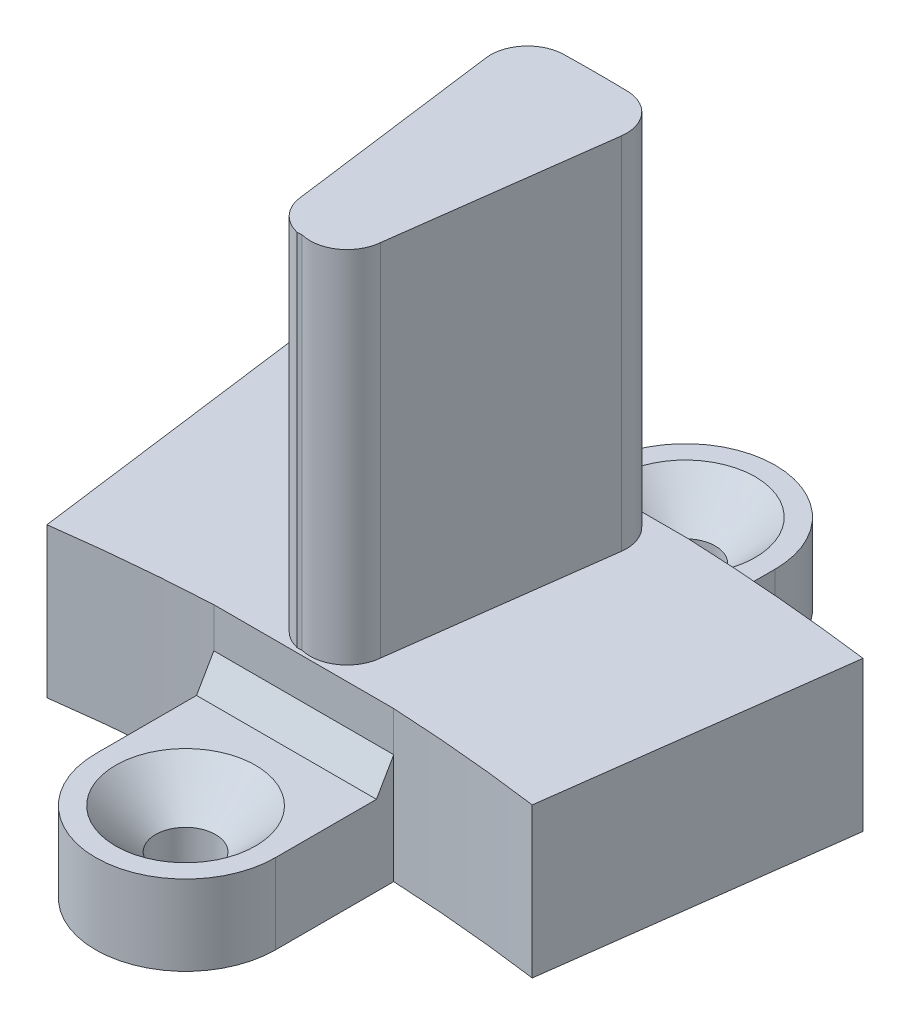
SolidWorks part; units mm, degrees
ref_plane "Front Plane" through (0, 0, 0) normal (0, 0, 1) x (1, 0, 0)
ref_plane "Top Plane" through (0, 0, 0) normal (0, 1, 0) x (1, 0, 0)
ref_plane "Right Plane" through (0, 0, 0) normal (1, 0, 0) x (0, 0, -1)
sketch "Sketch1" plane through (0, 0, 0) normal (0, 1, 0) x (1, 0, 0)
  line L0 (-42.0952, 101.6267) -> (-34.716, 83.8117) construction
  line L1 (34.716, 83.8117) -> (42.0952, 101.6267) construction
  line L2 (0, 90.7172) -> (0, 171.0298) construction
  line L3 (-34.716, 83.8117) -> (0, 0) construction
  line L4 (0, 0) -> (0, 90.7172) construction
  line L5 (0, 0) -> (34.716, 83.8117) construction
  line L6 (14.0642, 106.8282) -> (12.1389, 92.2044) construction
  line L7 (-14.0642, 106.8282) -> (-12.1389, 92.2044) construction
  line L8 (-14.0642, 106.8282) -> (-12.1389, 92.2044)
  line L9 (12.1389, 92.2044) -> (14.0642, 106.8282)
  line L10 (13.0994, 99.5) -> (-13.0994, 99.5) construction
  line L11 (-4.5, 112) -> (-4.5, 109.9079)
  line L12 (4.5, 112) -> (4.5, 109.9079)
  line L13 (4.5, 87) -> (4.5, 89.0921)
  line L14 (-4.5, 87) -> (-4.5, 89.0921)
  line L15 (-4.5, 89.0921) -> (-4.5, 90.6055)
  line L16 (4.5, 89.0921) -> (4.5, 90.6055)
  line L17 (-4.5, 90.6055) -> (-4.5, 92.9142)
  line L18 (4.5, 90.6055) -> (4.5, 92.9142)
  line L19 (-4.5, 109.9079) -> (-4.5, 107.6389)
  line L20 (4.5, 109.9079) -> (4.5, 107.6389)
  line L21 (12.1389, 92.2044) -> (11.841, 89.9411) construction
  line L22 (11.841, 89.9411) -> (0, 0) construction
  line L23 (11.841, 89.9411) -> (12.1389, 92.2044) construction
  line L24 (-12.1389, 92.2044) -> (-11.841, 89.9411) construction
  line L25 (-11.841, 89.9411) -> (0, 0) construction
  line L26 (-12.1389, 92.2044) -> (-11.841, 89.9411) construction
  line L27 (14.3579, 109.0589) -> (14.0642, 106.8282) construction
  line L28 (14.0642, 106.8282) -> (14.3579, 109.0589) construction
  line L29 (-14.3579, 109.0589) -> (-14.0642, 106.8282) construction
  line L30 (-14.3579, 109.0589) -> (-14.0642, 106.8282) construction
  arc A0 (-14.3579, 109.0589) -> (14.3579, 109.0589) centre (0, 0) ccw construction
  arc A1 (42.0952, 101.6267) -> (14.3579, 109.0589) centre (0, 0) ccw construction
  arc A3 (14.3579, 109.0589) -> (4.5, 109.9079) centre (0, 0) ccw construction
  circle A5 centre (0, 112) radius 1.5
  circle A6 centre (0, 87) radius 1.5
  arc A7 (-4.5, 112) -> (4.5, 112) centre (0, 112) cw
  arc A8 (0, 110) -> (-4.5, 109.9079) centre (0, 0) ccw construction
  arc A9 (-4.5, 109.9079) -> (-14.3579, 109.0589) centre (0, 0) ccw construction
  arc A10 (0, 110) -> (-4.5, 109.9079) centre (0, 0) ccw construction
  arc A11 (0, 110) -> (-4.5, 109.9079) centre (0, 0) ccw construction
  arc A12 (-14.3579, 109.0589) -> (-42.0952, 101.6267) centre (0, 0) ccw construction
  arc A13 (4.5, 109.9079) -> (0, 110) centre (0, 0) ccw construction
  arc A14 (4.5, 109.9079) -> (0, 110) centre (0, 0) ccw construction
  arc A15 (4.5, 109.9079) -> (0, 110) centre (0, 0) ccw construction
  arc A16 (-4.5, 87) -> (4.5, 87) centre (0, 87) ccw
  arc A18 (14.3579, 109.0589) -> (4.5, 109.9079) centre (0, 0) ccw construction
  arc A23 (-4.5, 92.9142) -> (-12.1389, 92.2044) centre (0, 3.0268) ccw
  arc A24 (12.1389, 92.2044) -> (4.5, 92.9142) centre (0, 3.0268) ccw
  arc A25 (14.0642, 106.8282) -> (4.5, 107.6389) centre (0, -2.269) ccw
  arc A26 (-4.5, 107.6389) -> (-14.0642, 106.8282) centre (0, -2.269) ccw
  arc A27 (14.3579, 109.0589) -> (4.5, 109.9079) centre (0, 0) ccw construction
  arc A28 (-4.5, 109.9079) -> (-14.3579, 109.0589) centre (0, 0) ccw construction
  arc A29 (-4.5, 109.9079) -> (-14.3579, 109.0589) centre (0, 0) ccw construction
  dimension "D1" = 220
  dimension "D2" = 45
  dimension "D3" = 90
  dimension "D4" = 15
  dimension "D5" = 3
  dimension "D7" = 9
  dimension "D11" = 110
  dimension "D6" = 12.5
  dimension "D8" = 112
  dimension "D9" = 17
  dimension "D10" = 2.25
extrude "Boss-Extrude1" add sketch "Sketch1" along normal mid plane 7.5
sketch "Sketch3" plane through (0, 3.75, 0) normal (0, 1, 0) x (1, 0, 0)
  line L0 (0, 100) -> (0, 141.737) construction
  line L1 (2.3796, 94.7219) -> (3.7828, 105.38) construction
  line L2 (-15.3858, 117.2955) -> (-10.85, 82.8428) construction
  line L3 (-10.85, 82.8428) -> (10.85, 82.8428) construction
  line L4 (10.85, 82.8428) -> (15.3858, 117.2955) construction
  line L5 (-3.7828, 105.38) -> (-2.3796, 94.7219) construction
  line L6 (-0.14, 94.9379) -> (0.14, 94.9379) construction
  line L7 (-1.55, 105.6579) -> (1.55, 105.6579) construction
  line L8 (0, 0) -> (0, 185.4872) construction
  line L9 (0, 0) -> (-64.4427, 155.5785) construction
  line L10 (16.8206, 117.1376) -> (12.3725, 82.6735) construction
  line L11 (12.3725, 82.6735) -> (33.3473, 77.1105) construction
  line L12 (33.3473, 77.1105) -> (46.5638, 109.249) construction
  line L15 (2.1809, 94.7445) -> (3.5844, 105.4054) construction
  line L16 (-3.5844, 105.4054) -> (-2.1809, 94.7445) construction
  line L17 (-33.3473, 77.1105) -> (-46.5638, 109.249) construction
  line L18 (-12.3725, 82.6735) -> (-33.3473, 77.1105) construction
  line L19 (-16.8206, 117.1376) -> (-12.3725, 82.6735) construction
  line L22 (0.112, -6.3136) -> (-38.6692, 138.4201) construction
  line L23 (28.2053, 90.7642) -> (32.2939, 100.7063) [skipped]
  line L24 (24.9812, 102.6458) -> (23.6052, 91.9842) [skipped]
  line L25 (28.5631, 91.754) -> (32.6664, 101.6901) construction
  line L26 (25.3566, 103.6405) -> (23.9648, 92.9809) construction
  line L27 (1.9821, 94.7669) -> (3.386, 105.4307)
  line L28 (-3.386, 105.4307) -> (-1.9821, 94.7669)
  line L29 (-25.3566, 103.6405) -> (-23.9648, 92.9809) construction
  line L30 (-28.5631, 91.754) -> (-32.6664, 101.6901) construction
  line L31 (1.3856, 94.8327) -> (2.7908, 105.5065) construction
  line L32 (-2.7908, 105.5065) -> (-1.3856, 94.8327) construction
  line L33 (27.6312, 92.1173) -> (31.7406, 102.0681) construction
  line L34 (26.3477, 103.507) -> (24.9538, 92.8317) construction
  line L35 (-27.6312, 92.1173) -> (-31.7406, 102.0681) construction
  line L36 (-26.3477, 103.507) -> (-24.9538, 92.8317) construction
  arc A0 (3.5844, 105.4054) -> (1.6433, 107.7058) centre (1.55, 105.6579) ccw construction
  arc A1 (15.3858, 117.2955) -> (-15.3858, 117.2955) centre (0, 34.7165) ccw construction
  arc A2 (-2.3796, 94.7219) -> (-0.5847, 92.7323) centre (-0.14, 94.9379) ccw construction
  arc A3 (-0.3542, 92.7429) -> (2.3796, 94.7219) centre (0.14, 94.9379) ccw construction
  arc A4 (-0.3542, 92.7429) -> (-0.5847, 92.7323) centre (4.1141, -7.1572) ccw construction
  arc A5 (3.7828, 105.38) -> (1.65, 107.9057) centre (1.55, 105.6579) ccw construction
  arc A6 (1.65, 107.9057) -> (-1.65, 107.9057) centre (0, 34.9826) ccw construction
  arc A7 (-1.65, 107.9057) -> (-3.7828, 105.38) centre (-1.55, 105.6579) ccw construction
  arc A8 (46.5638, 109.249) -> (16.8206, 117.1376) centre (10.5223, 33.3741) ccw construction
  arc A15 (-46.5638, 109.249) -> (-16.8206, 117.1376) centre (-10.5223, 33.3741) cw construction
  arc A22 (32.2939, 100.7063) -> (30.8799, 103.6944) centre (30.207, 101.5473) ccw [skipped]
  arc A23 (30.8799, 103.6944) -> (27.6902, 104.5404) centre (10.5905, 33.6312) ccw [skipped]
  arc A24 (27.6902, 104.5404) -> (24.9812, 102.6458) centre (27.2106, 102.3421) ccw [skipped]
  arc A25 (23.6052, 91.9842) -> (24.83, 89.6009) centre (25.8253, 91.6188) ccw [skipped]
  arc A26 (25.0555, 89.5521) -> (24.83, 89.6009) centre (3.7641, -8.155) ccw [skipped]
  arc A27 (25.0555, 89.5521) -> (28.2053, 90.7642) centre (26.0959, 91.5471) ccw [skipped]
  arc A28 (32.6664, 101.6901) -> (31.2569, 104.6803) centre (30.5808, 102.5342) ccw construction
  arc A29 (31.2569, 104.6803) -> (28.0684, 105.531) centre (10.8634, 34.6473) ccw construction
  arc A30 (28.0684, 105.531) -> (25.3566, 103.6405) centre (27.5856, 103.3334) ccw construction
  arc A31 (23.9648, 92.9809) -> (25.1861, 90.5958) centre (26.1843, 92.6123) ccw construction
  arc A32 (25.4115, 90.5466) -> (25.1861, 90.5958) centre (3.975, -7.1287) ccw construction
  arc A33 (25.4115, 90.5466) -> (28.5631, 91.754) centre (26.4549, 92.5401) ccw construction
  arc A34 (-25.4115, 90.5466) -> (-28.5631, 91.754) centre (-26.4549, 92.5401) cw construction
  arc A35 (-25.4115, 90.5466) -> (-25.1861, 90.5958) centre (-3.975, -7.1287) cw construction
  arc A36 (-23.9648, 92.9809) -> (-25.1861, 90.5958) centre (-26.1843, 92.6123) cw construction
  arc A37 (-28.0684, 105.531) -> (-25.3566, 103.6405) centre (-27.5856, 103.3334) cw construction
  arc A38 (-31.2569, 104.6803) -> (-28.0684, 105.531) centre (-10.8634, 34.6473) cw construction
  arc A39 (-32.6664, 101.6901) -> (-31.2569, 104.6803) centre (-30.5808, 102.5342) cw construction
  arc A40 (2.7908, 105.5065) -> (1.6149, 106.9062) centre (1.55, 105.6579) ccw construction
  arc A41 (1.6149, 106.9062) -> (-1.6149, 106.9062) centre (0, 34.9826) ccw construction
  arc A42 (-1.6149, 106.9062) -> (-2.7908, 105.5065) centre (-1.55, 105.6579) ccw construction
  arc A43 (-1.3856, 94.8327) -> (-0.4895, 93.7378) centre (-0.14, 94.9379) ccw construction
  arc A44 (-0.2449, 93.7486) -> (-0.4895, 93.7378) centre (4.1141, -7.1572) ccw construction
  arc A45 (-0.2449, 93.7486) -> (1.3856, 94.8327) centre (0.14, 94.9379) ccw construction
  arc A46 (31.7406, 102.0681) -> (30.9653, 103.7236) centre (30.5808, 102.5342) ccw construction
  arc A47 (30.9653, 103.7236) -> (27.8446, 104.5563) centre (10.8634, 34.6473) ccw construction
  arc A48 (27.8446, 104.5563) -> (26.3477, 103.507) centre (27.5856, 103.3334) ccw construction
  arc A49 (24.9538, 92.8317) -> (25.5372, 91.5428) centre (26.1843, 92.6123) ccw construction
  arc A50 (25.7764, 91.4902) -> (25.5372, 91.5428) centre (3.975, -7.1287) ccw construction
  arc A51 (25.7764, 91.4902) -> (27.6312, 92.1173) centre (26.4549, 92.5401) ccw construction
  arc A52 (-25.7764, 91.4902) -> (-27.6312, 92.1173) centre (-26.4549, 92.5401) cw construction
  arc A53 (-31.7406, 102.0681) -> (-30.9653, 103.7236) centre (-30.5808, 102.5342) cw construction
  arc A54 (-30.9653, 103.7236) -> (-27.8446, 104.5563) centre (-10.8634, 34.6473) cw construction
  arc A55 (-27.8446, 104.5563) -> (-26.3477, 103.507) centre (-27.5856, 103.3334) cw construction
  arc A56 (-24.9538, 92.8317) -> (-25.5372, 91.5428) centre (-26.1843, 92.6123) cw construction
  arc A57 (-25.7764, 91.4902) -> (-25.5372, 91.5428) centre (-3.975, -7.1287) cw construction
  arc A58 (1.6433, 107.7058) -> (-1.6433, 107.7058) centre (0, 34.9826) ccw construction
  arc A59 (-1.6433, 107.7058) -> (-3.5844, 105.4054) centre (-1.55, 105.6579) ccw construction
  arc A60 (-2.1809, 94.7445) -> (-0.5688, 92.9333) centre (-0.14, 94.9379) ccw construction
  arc A61 (-0.3358, 92.9439) -> (-0.5688, 92.9333) centre (4.1141, -7.1572) ccw construction
  arc A62 (-0.3358, 92.9439) -> (2.1809, 94.7445) centre (0.14, 94.9379) ccw construction
  arc A63 (3.386, 105.4307) -> (1.6364, 107.5059) centre (1.55, 105.6579) ccw
  arc A64 (1.6364, 107.5059) -> (-1.6364, 107.5059) centre (0, 34.9826) ccw
  arc A65 (-1.6364, 107.5059) -> (-3.386, 105.4307) centre (-1.55, 105.6579) ccw
  arc A66 (-1.9821, 94.7669) -> (-0.5516, 93.1343) centre (-0.14, 94.9379) ccw
  arc A67 (-0.3159, 93.145) -> (-0.5516, 93.1343) centre (4.1141, -7.1572) ccw
  arc A68 (-0.3159, 93.145) -> (1.9821, 94.7669) centre (0.14, 94.9379) ccw
  point P25 (0, 105.6579)
  point P26 (0, 94.9379)
  point P27 (0, 82.8428)
  dimension "D3" = 100
  dimension "D4" = 2.25
  dimension "D5" = 10.72
  dimension "D6" = 15
  dimension "D7" = 2.25
  dimension "D11" = 84
  dimension "D15" = 22.5
  dimension "D21" = 1
  dimension "D1" = 3.1
  dimension "D2" = 0.28
  dimension "D8" = 10.75
  dimension "D9" = 15
  dimension "D10" = 34.75
  dimension "D12" = 21.7
  dimension "D13" = 15
  dimension "D14" = 90
  dimension "D17" = 0.8
  dimension "D18" = 15
  dimension "D20" = 0.2
  dimension "D16" = 2
  dimension "D19" = 2
extrude "Boss-Extrude2" add sketch "Sketch3" along normal blind 18 and the other way up to surface (7.5 mm away) other way up to face at (0, -3.75, -99.7952)
sketch "Sketch4" plane through (0, 3.75, 0) normal (0, 1, 0) x (1, 0, 0)
  line L3 (13.1016, 99.5163) -> (-13.1016, 99.5163) construction
  line L4 (12.1389, 92.2044) -> (14.0642, 106.8282) construction
  line L5 (-14.0642, 106.8282) -> (-12.1389, 92.2044) construction
  line L12 (-4.5, 91.3937) -> (-4.5, 87.0326)
  line L13 (4.5, 107.6389) -> (-4.5, 107.6389)
  line L14 (-4.5, 107.6389) -> (-4.5, 112)
  line L15 (4.5, 112) -> (4.5, 107.6389)
  line L16 (4.5, 91.3937) -> (-4.5, 91.3937) construction
  line L17 (4.5, 87.0326) -> (4.5, 91.3937)
  line L18 (-4.5, 91.3937) -> (-4.5, 92.9142)
  line L19 (-4.5, 92.9142) -> (4.5, 92.9142)
  line L20 (4.5, 92.9142) -> (4.5, 91.3937)
  circle A1 centre (0, 112) radius 1.5 construction
  circle A2 centre (0, 112) radius 1.5
  arc A6 (-4.5, 112) -> (4.5, 112) centre (0, 112) cw
  circle A8 centre (0, 87) radius 1.5 construction
  circle A9 centre (0, 87) radius 1.5
  arc A11 (-4.5, 87.0326) -> (4.5, 87.0326) centre (0, 86.9178) ccw
extrude "Cut-Extrude1" cut sketch "Sketch4" against normal blind 3.5 and the other way through all
chamfer "Chamfer1" distance 2 angle 45 2 edges at (0, 0.25, -85.5) (0, 0.25, -110.5)
chamfer "Chamfer2" distance 1.5 angle 30 2 edges at (0, 0.25, -107.6389) (0, 0.25, -92.9142) first distance on face at (0, 2, -107.6389) first distance on face at (0, 2, -92.9142)
